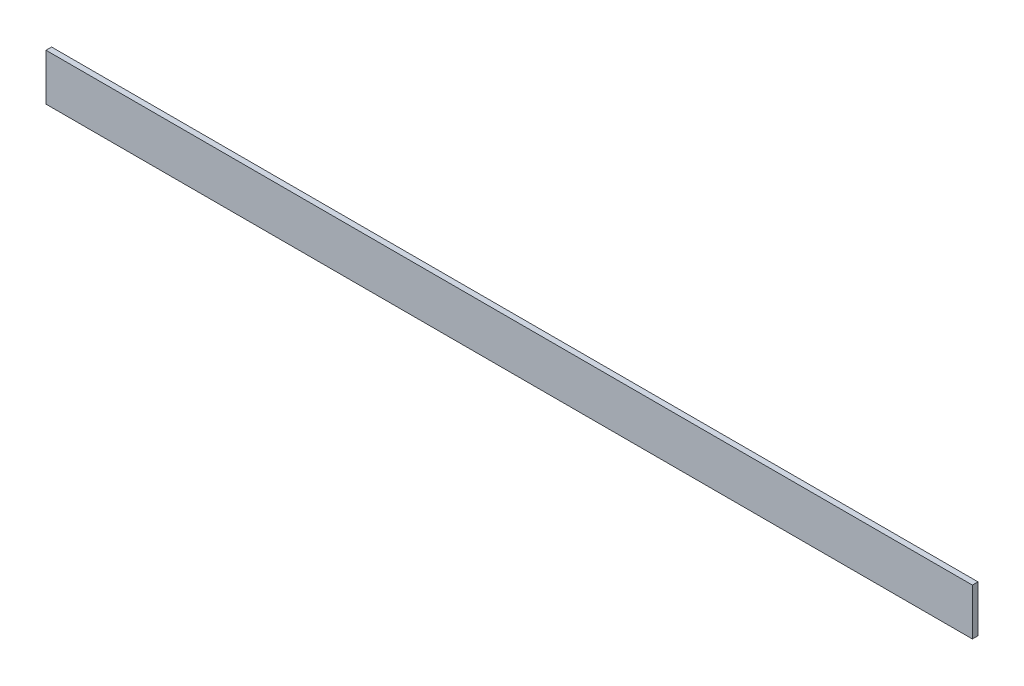
SolidWorks part; units mm, degrees
ref_plane "Спереди" through (0, 0, 0) normal (0, 0, 1) x (1, 0, 0)
ref_plane "Сверху" through (0, 0, 0) normal (0, 1, 0) x (1, 0, 0)
ref_plane "Справа" through (0, 0, 0) normal (1, 0, 0) x (0, 0, -1)
sketch "Эскиз1" plane through (0, 0, 0) normal (1, 0, 0) x (0, 0, -1)
  line L0 (0, 0) -> (25, 0)
  line L1 (0, 0) -> (0, 25)
extrude "Вытянуть-Тонкостенный1" add sketch "Эскиз1" along normal blind 496 thin thin type one direction wall 3
sketch "Эскиз2" plane through (0, 0, 0) normal (0, -1, 0) x (1, 0, 0)
  line L0 (248, 0) -> (248, -62.1579) construction
  line L1 (496, -25) -> (471, -25)
  line L2 (496, -25) -> (496, -3)
  line L3 (496, -3) -> (471, -3)
  line L4 (471, -25) -> (471, -3)
  line L5 (496, 0) -> (0, 0) construction
  line L6 (25, -25) -> (25, -3)
  line L7 (0, -3) -> (25, -3)
  line L8 (0, -25) -> (0, -3)
  line L9 (0, -25) -> (25, -25)
extrude "Вырез-Вытянуть1" cut sketch "Эскиз2" against normal through all
